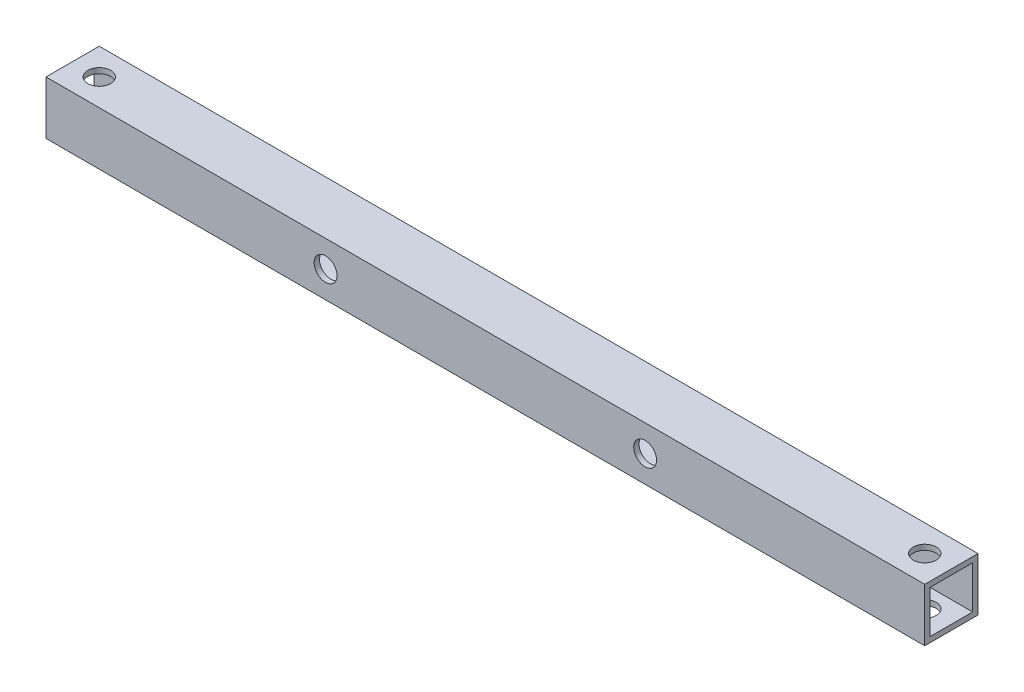
SolidWorks part; units mm, degrees
material "5052-H34"
ref_plane "正面" through (0, 0, 0) normal (0, 0, 1) x (1, 0, 0)
ref_plane "平面" through (0, 0, 0) normal (0, 1, 0) x (1, 0, 0)
ref_plane "右側面" through (0, 0, 0) normal (1, 0, 0) x (0, 0, -1)
sketch "ｽｹｯﾁ1" plane through (0, 0, 0) normal (1, 0, 0) x (0, 0, -1)
  line L1 (-5, 5) -> (5, 5)
  line L2 (-5, 5) -> (-5, -5)
  line L3 (-5, -5) -> (5, -5)
  line L4 (5, 5) -> (5, -5)
  line L5 (-5, 5) -> (5, -5) construction
  line L6 (-5, -5) -> (5, 5) construction
  point P0 (0, 0)
  dimension "D1" = 10
  dimension "D2" = 10
extrude "押し出し-薄板1" add sketch "ｽｹｯﾁ1" along normal blind 165 thin thin type one direction reverse wall 1
sketch "ｽｹｯﾁ3" plane through (0, 0, 5) normal (0, 0, 1) x (1, 0, 0)
  line L0 (82.5, 5) -> (82.5, -5) construction
  line L1 (165, 5) -> (0, 5) construction
  line L2 (165, -5) -> (0, -5) construction
  line L3 (0, 0) -> (52.5, 0) construction
  circle A0 centre (52.5, 0) radius 2.15
  circle A1 centre (112.5, 0) radius 2.15
  dimension "D2" = 4.3
  dimension "D1" = 60
extrude "ｶｯﾄ - 押し出し1" cut sketch "ｽｹｯﾁ3" against normal through all
sketch "ｽｹｯﾁ4" plane through (0, 5, 0) normal (0, 1, 0) x (1, 0, 0)
  line L0 (0, 0) -> (5, 0) construction
  line L1 (82.5, 5) -> (82.5, -5) construction
  line L2 (165, 5) -> (0, 5) construction
  line L3 (165, -5) -> (0, -5) construction
  circle A0 centre (5, 0) radius 2.15
  circle A1 centre (160, 0) radius 2.15
  dimension "D1" = 4.3
  dimension "D2" = 5
extrude "ｶｯﾄ - 押し出し2" cut sketch "ｽｹｯﾁ4" against normal through all
